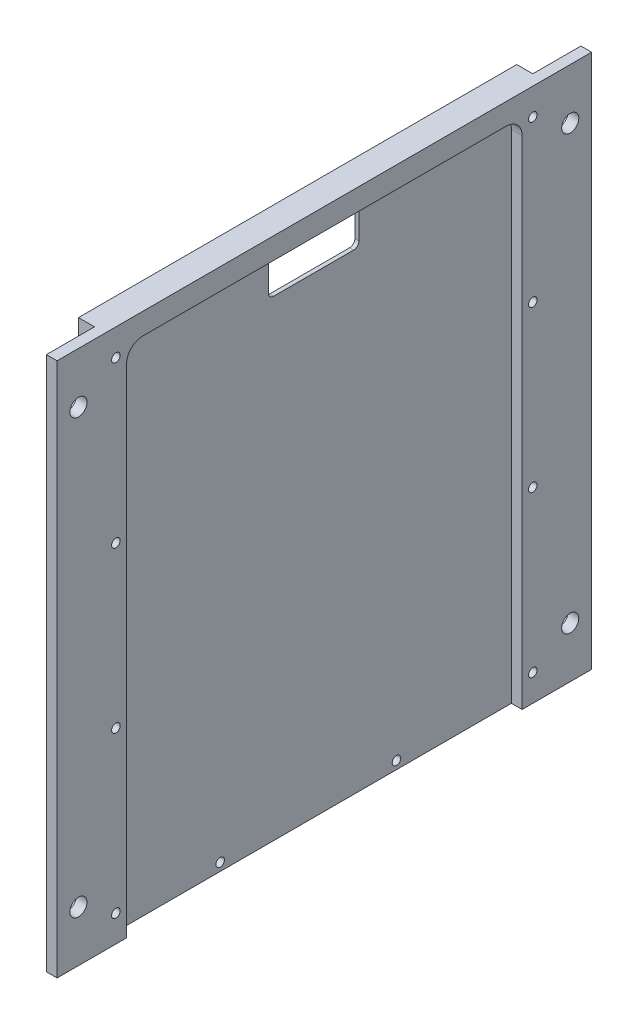
SolidWorks part; units mm, degrees
material "6061-T6 (SS)"
ref_plane "Front Plane" through (0, 0, 0) normal (0, 0, 1) x (1, 0, 0)
ref_plane "Top Plane" through (0, 0, 0) normal (0, 1, 0) x (1, 0, 0)
ref_plane "Right Plane" through (0, 0, 0) normal (1, 0, 0) x (0, 0, -1)
ref_plane "Plane1" through (4.25, 0, 0) normal (1, 0, 0) x (0, 0, -1)
sketch "Sketch1" plane through (4.25, 0, 0) normal (1, 0, 0) x (0, 0, -1)
  line L0 (-4.25, 0) -> (4.25, 0)
  line L1 (4.25, 0) -> (4.25, 227)
  line L2 (4.25, 227) -> (-4.25, 227)
  line L3 (-4.25, 227) -> (-4.25, 0)
  dimension "D1" = 227
  dimension "D2" = 8.5
  dimension "D3" = 4.25
  dimension "D4" = 227
extrude "Boss-Extrude1" add sketch "Sketch1" against normal blind 8.5
ref_plane "Plane2" through (-4.25, 0, 0) normal (-1, 0, 0) x (0, -1, 0)
sketch "Sketch2" plane through (-4.25, 0, 0) normal (-1, 0, 0) x (0, -1, 0)
  line L0 (-6.5, -87.25) -> (-6.5, -4.25)
  line L1 (-6.5, -4.25) -> (-220.5, -4.25)
  line L2 (-220.5, -4.25) -> (-220.5, -87.25)
  line L3 (-220.5, -87.25) -> (-227, -87.25)
  line L4 (-227, -87.25) -> (-227, -95.75)
  line L5 (-227, -95.75) -> (0, -95.75)
  line L6 (0, -95.75) -> (0, -87.25)
  line L7 (0, -87.25) -> (-6.5, -87.25)
  line L8 (0, -4.25) -> (-227, -4.25) construction
  dimension "D1" = 91.5
  dimension "D2" = 6.5
  dimension "D3" = 83
  dimension "D4" = 8.5
  dimension "D5" = 214
extrude "Boss-Extrude2" add sketch "Sketch2" against normal blind 2
sketch "Sketch3" plane through (-2.25, 0, 0) normal (1, 0, 0) x (0, 0, -1)
  line L0 (87.25, 0) -> (87.25, 227)
  line L1 (87.25, 227) -> (95.75, 227)
  line L2 (95.75, 227) -> (95.75, 0)
  line L3 (95.75, 0) -> (87.25, 0)
extrude "Boss-Extrude3" add sketch "Sketch3" along normal blind 6.5
ref_plane "Z_midplane" through (0, 113.5, 0) normal (0, 1, 0) x (1, 0, 0)
sketch "Sketch4" plane through (-4.25, 0, 0) normal (-1, 0, 0) x (0, 0, 1)
  line L0 (-4.75, 6.5) -> (-86.75, 6.5)
  line L1 (-86.75, 6.5) -> (-86.75, 220.5)
  line L2 (-86.75, 220.5) -> (-4.75, 220.5)
  line L3 (-4.75, 220.5) -> (-4.75, 6.5)
extrude "Boss-Extrude4" add sketch "Sketch4" along normal blind 3
sketch "Sketch5" plane through (-2.25, 0, 0) normal (1, 0, 0) x (0, 0, -1)
  line L0 (8.75, 10.5) -> (82.75, 10.5)
  line L1 (82.75, 10.5) -> (82.75, 216.5)
  line L2 (82.75, 216.5) -> (8.75, 216.5)
  line L3 (8.75, 216.5) -> (8.75, 10.5)
  line L4 (87.25, 6.5) -> (4.25, 6.5) construction
  line L5 (4.75, 6.5) -> (4.75, 220.5) construction
  line L6 (86.75, 220.5) -> (86.75, 6.5) construction
  line L7 (4.75, 220.5) -> (86.75, 220.5) construction
  dimension "D1" = 4
  dimension "D2" = 4
  dimension "D3" = 4
  dimension "D4" = 4
extrude "Cut-Extrude1" cut sketch "Sketch5" against normal through all
hole_wizard "M2x0.4 Tapped Hole1" positions "Sketch27" profile "Sketch26" tap size "M2x0.4" standard "ANSI Metric" end condition through all
sketch "Sketch27" plane through (-7.25, 0, 0) normal (-1, 0, 0) x (0, 0, 1)
  line L0 (-86.75, 6.5) -> (-4.75, 6.5) construction
  line L2 (-45.75, 10.5) -> (-45.75, 216.5) construction
  line L3 (-8.75, 10.5) -> (-82.75, 10.5) construction
  line L4 (-82.75, 216.5) -> (-8.75, 216.5) construction
  line L6 (-8.75, 113.5) -> (-82.75, 113.5) construction
  line L7 (-8.75, 216.5) -> (-8.75, 10.5) construction
  line L8 (-82.75, 10.5) -> (-82.75, 216.5) construction
  line L9 (-8.75, 11.5) -> (-4.75, 11.5) construction
  line L10 (-4.75, 6.5) -> (-4.75, 220.5) construction
  point P0 (-6.75, 11.5)
  point P31 (-6.75, 41.5)
  point P32 (-6.75, 71.5)
  point P33 (-6.75, 101.5)
  point P54 (-84.75, 11.5)
  point P55 (-84.75, 41.5)
  point P56 (-84.75, 71.5)
  point P57 (-84.75, 101.5)
  point P60 (-84.75, 125.5)
  point P61 (-84.75, 155.5)
  point P62 (-84.75, 185.5)
  point P63 (-84.75, 215.5)
  point P65 (-6.75, 125.5)
  point P66 (-6.75, 155.5)
  point P67 (-6.75, 185.5)
  point P68 (-6.75, 215.5)
  point P81 (-6.75, 11.5)
  dimension "D1" = 5
  dimension "D4" = 30
  dimension "D3" = 4
sketch "Sketch26" plane through (-7.25, 11.5, -6.75) normal (0, 1, 0) x (0, 0, 1)
  line L0 (0, 0) -> (0, 11.5)
  line L1 (0, 11.5) -> (0.8, 11.5)
  line L2 (0.8, 11.5) -> (0.8, 0)
  line L5 (0.8, 0) -> (0, 0)
  line L11 (0, -6.35) -> (0, 107.95) construction
  dimension "Thru Tap Drill Dia." = 1.6
  dimension "Thru Tap Drill Depth" = 11.5
cosmetic thread "Hole Thread1" parameters "D2"=2
cosmetic thread "Hole Thread2" parameters "D2"=2
cosmetic thread "Hole Thread3" parameters "D2"=2
cosmetic thread "Hole Thread4" parameters "D2"=2
cosmetic thread "Hole Thread5" parameters "D2"=2
cosmetic thread "Hole Thread6" parameters "D2"=2
cosmetic thread "Hole Thread7" parameters "D2"=2
cosmetic thread "Hole Thread8" parameters "D2"=2
cosmetic thread "Hole Thread9" parameters "D2"=2
cosmetic thread "Hole Thread10" parameters "D2"=2
cosmetic thread "Hole Thread11" parameters "D2"=2
cosmetic thread "Hole Thread12" parameters "D2"=2
cosmetic thread "Hole Thread13" parameters "D2"=2
cosmetic thread "Hole Thread14" parameters "D2"=2
cosmetic thread "Hole Thread15" parameters "D2"=2
cosmetic thread "Hole Thread16" parameters "D2"=2
fillet "Fillet2" radius 3 4 edges at (-4.75, 10.5, -8.75) (-4.75, 216.5, -82.75) (-4.75, 216.5, -8.75) (-4.75, 10.5, -82.75) tangent propagation no
fillet "Fillet12" radius 2 1 edges type face fillet first side face at (-6.5, 140.25, -86.75) second side face at (-4.75, 6.5, -45.8125)
ref_plane "Y_midplane" through (0, 0, -45.75) normal (0, 0, 1) x (1, 0, 0)
sketch "Sketch43" plane through (-7.25, 0, 0) normal (-1, 0, 0) x (0, 0, 1)
  line L0 (-45.75, 10.5) -> (-45.75, 216.5) construction
  line L1 (-27.75, 10.5) -> (-30.75, 10.5)
  line L2 (-27.75, 10.5) -> (-27.75, 216.5)
  line L3 (-27.75, 216.5) -> (-30.75, 216.5)
  line L4 (-30.75, 10.5) -> (-30.75, 216.5)
  line L5 (-11.75, 10.5) -> (-79.75, 10.5) construction
  line L6 (-79.75, 216.5) -> (-11.75, 216.5) construction
  line L7 (-63.75, 10.5) -> (-60.75, 10.5)
  line L8 (-63.75, 10.5) -> (-63.75, 216.5)
  line L9 (-63.75, 216.5) -> (-60.75, 216.5)
  line L10 (-60.75, 10.5) -> (-60.75, 216.5)
  dimension "D1" = 3
  dimension "D2" = 30
extrude "Boss-Extrude6" add sketch "Sketch43" against normal blind 3
sketch "Sketch44" plane through (-7.25, 0, 0) normal (-1, 0, 0) x (0, 0, 1)
  line L0 (-8.75, 213.5) -> (-8.75, 13.5) construction
  line L1 (-8.75, 35.8) -> (-82.75, 35.8)
  line L2 (-8.75, 35.8) -> (-8.75, 38.8)
  line L3 (-8.75, 38.8) -> (-82.75, 38.8)
  line L4 (-82.75, 35.8) -> (-82.75, 38.8)
  line L5 (-8.75, 75.8) -> (-82.75, 75.8)
  line L6 (-8.75, 75.8) -> (-8.75, 78.8)
  line L7 (-8.75, 78.8) -> (-82.75, 78.8)
  line L8 (-82.75, 75.8) -> (-82.75, 78.8)
  line L9 (-8.75, 103.5) -> (-82.75, 103.5)
  line L10 (-8.75, 103.5) -> (-8.75, 106.5)
  line L11 (-8.75, 106.5) -> (-82.75, 106.5)
  line L12 (-82.75, 103.5) -> (-82.75, 106.5)
  line L13 (-82.75, 13.5) -> (-82.75, 213.5) construction
  line L14 (-84.75, 6.5) -> (-4.75, 6.5) construction
  line L15 (-8.75, 113.5) -> (-82.75, 113.5) construction
  line L16 (-8.75, 191.2) -> (-8.75, 188.2)
  line L17 (-8.75, 191.2) -> (-82.75, 191.2)
  line L18 (-82.75, 191.2) -> (-82.75, 188.2)
  line L19 (-8.75, 188.2) -> (-82.75, 188.2)
  line L20 (-8.75, 151.2) -> (-8.75, 148.2)
  line L21 (-8.75, 151.2) -> (-82.75, 151.2)
  line L22 (-82.75, 151.2) -> (-82.75, 148.2)
  line L23 (-8.75, 148.2) -> (-82.75, 148.2)
  line L24 (-8.75, 123.5) -> (-8.75, 120.5)
  line L25 (-8.75, 123.5) -> (-82.75, 123.5)
  line L26 (-82.75, 123.5) -> (-82.75, 120.5)
  line L27 (-8.75, 120.5) -> (-82.75, 120.5)
  dimension "D1" = 3
  dimension "D2" = 29.3
  dimension "D3" = 40
  dimension "D4" = 100
extrude "Boss-Extrude7" add sketch "Sketch44" against normal up to surface (3 mm away) up to face at (-4.25, 113.5, -29.25)
fillet "Fillet4" radius 3 80 edges at (-5.75, 188.2, -8.75) (-5.75, 216.5, -60.75) (-5.75, 35.8, -82.75) (-5.75, 38.8, -82.75) (-5.75, 75.8, -82.75) (-5.75, 78.8, -82.75) (-5.75, 103.5, -82.75) (-5.75, 106.5, -82.75) (-5.75, 120.5, -82.75) (-5.75, 123.5, -82.75) (-5.75, 10.5, -60.75) (-5.75, 10.5, -63.75) (-5.75, 10.5, -27.75) (-5.75, 10.5, -30.75) (-5.75, 35.8, -8.75) (-5.75, 38.8, -8.75) (-5.75, 75.8, -8.75) (-5.75, 78.8, -8.75) (-5.75, 103.5, -8.75) (-5.75, 106.5, -8.75) (-5.75, 123.5, -8.75) (-5.75, 120.5, -8.75) (-5.75, 151.2, -8.75) (-5.75, 148.2, -8.75) (-5.75, 216.5, -27.75) (-5.75, 216.5, -63.75) (-5.75, 216.5, -30.75) (-5.75, 191.2, -8.75) (-5.75, 148.2, -82.75) (-5.75, 151.2, -82.75) (-5.75, 188.2, -82.75) (-5.75, 191.2, -82.75) (-5.75, 191.2, -60.75) (-5.75, 188.2, -60.75) (-5.75, 191.2, -63.75) (-5.75, 188.2, -63.75) (-5.75, 191.2, -27.75) (-5.75, 191.2, -30.75) (-5.75, 188.2, -27.75) (-5.75, 188.2, -30.75) (-5.75, 151.2, -27.75) (-5.75, 151.2, -30.75) (-5.75, 148.2, -27.75) (-5.75, 148.2, -30.75) (-5.75, 151.2, -60.75) (-5.75, 148.2, -60.75) (-5.75, 151.2, -63.75) (-5.75, 148.2, -63.75) (-5.75, 123.5, -27.75) (-5.75, 123.5, -30.75) (-5.75, 120.5, -27.75) (-5.75, 120.5, -30.75) (-5.75, 103.5, -27.75) (-5.75, 103.5, -30.75) (-5.75, 106.5, -27.75) (-5.75, 106.5, -30.75) (-5.75, 123.5, -60.75) (-5.75, 120.5, -60.75) (-5.75, 123.5, -63.75) (-5.75, 120.5, -63.75) (-5.75, 103.5, -60.75) (-5.75, 106.5, -60.75) (-5.75, 103.5, -63.75) (-5.75, 106.5, -63.75) (-5.75, 78.8, -30.75) (-5.75, 75.8, -27.75) (-5.75, 75.8, -30.75) (-5.75, 78.8, -27.75) (-5.75, 75.8, -60.75) (-5.75, 78.8, -60.75) (-5.75, 75.8, -63.75) (-5.75, 78.8, -63.75) (-5.75, 35.8, -27.75) (-5.75, 35.8, -30.75) (-5.75, 38.8, -27.75) (-5.75, 38.8, -30.75) (-5.75, 35.8, -63.75) (-5.75, 35.8, -60.75) (-5.75, 38.8, -63.75) (-5.75, 38.8, -60.75) tangent propagation no
sketch "Sketch50" plane through (-4.25, 0, 0) normal (1, 0, 0) x (0, 0, -1)
  line L0 (79.75, 216.5) -> (11.75, 216.5) construction
  line L1 (8.75, 213.5) -> (8.75, 13.5) construction
  line L2 (11.75, 10.5) -> (79.75, 10.5) construction
  line L3 (82.75, 13.5) -> (82.75, 213.5) construction
  line L4 (79.75, 216.5) -> (11.75, 216.5)
  line L5 (8.75, 213.5) -> (8.75, 13.5)
  line L6 (11.75, 10.5) -> (79.75, 10.5)
  line L7 (82.75, 13.5) -> (82.75, 213.5)
  arc A0 (82.75, 213.5) -> (79.75, 216.5) centre (79.75, 213.5) ccw construction
  arc A1 (11.75, 216.5) -> (8.75, 213.5) centre (11.75, 213.5) ccw construction
  arc A2 (8.75, 13.5) -> (11.75, 10.5) centre (11.75, 13.5) ccw construction
  arc A3 (79.75, 10.5) -> (82.75, 13.5) centre (79.75, 13.5) ccw construction
  arc A4 (82.75, 213.5) -> (79.75, 216.5) centre (79.75, 213.5) ccw
  arc A5 (11.75, 216.5) -> (8.75, 213.5) centre (11.75, 213.5) ccw
  arc A6 (8.75, 13.5) -> (11.75, 10.5) centre (11.75, 13.5) ccw
  arc A7 (79.75, 10.5) -> (82.75, 13.5) centre (79.75, 13.5) ccw
extrude "webExtrude" add sketch "Sketch50" against normal blind 0.75
sketch "Sketch51" plane through (-5, 0, 0) normal (-1, 0, 0) x (0, 0, 1)
  line L0 (-57.75, 216.5) -> (-33.75, 216.5) construction
  line L1 (-54.225, 216.5) -> (-37.275, 216.5)
  line L2 (-54.225, 216.5) -> (-54.225, 208.7)
  line L3 (-54.225, 208.7) -> (-37.275, 208.7)
  line L4 (-37.275, 216.5) -> (-37.275, 208.7)
  point P4 (-45.75, 216.5)
  dimension "D1" = 7.8
  dimension "D2" = 16.95
extrude "12pinCutout" cut sketch "Sketch51" against normal through all both and the other way through all
mirror "Mirror10" about plane through (0, 113.5, 0) normal (0, 1, 0) of "12pinCutout"
fillet "Fillet18" radius 1 8 edges at (-4.625, 216.5, -37.275) (-4.625, 216.5, -54.225) (-4.625, 208.7, -54.225) (-4.625, 208.7, -37.275) (-4.625, 10.5, -37.275) (-4.625, 18.3, -37.275) (-4.625, 18.3, -54.225) (-4.625, 10.5, -54.225)
hole_wizard "M2x0.4 Tapped Hole2" positions "Sketch45" profile "Sketch46" tap size "M2x0.4" standard "ANSI Metric" end condition through all
sketch "Sketch45" plane through (-7.25, 0, 0) normal (-1, 0, 0) x (0, 0, 1)
  line L0 (-44.75, 6.5) -> (-44.75, 220.5) construction
  line L1 (-84.75, 6.5) -> (-4.75, 6.5) construction
  line L20 (-4.75, 113.5) -> (-86.75, 113.5) construction
  line L21 (-4.75, 6.5) -> (-4.75, 220.5) construction
  line L23 (-62.25, 75.8) -> (-62.25, 78.8) construction
  line L24 (-79.75, 75.8) -> (-66.75, 75.8) construction
  line L25 (-66.75, 78.8) -> (-79.75, 78.8) construction
  line L27 (-60.75, 77.3) -> (-63.75, 77.3) construction
  line L28 (-60.75, 41.8) -> (-60.75, 72.8) construction
  line L29 (-63.75, 72.8) -> (-63.75, 41.8) construction
  line L30 (-79.75, 216.5) -> (-11.75, 216.5) construction
  line L31 (-87.25, 227) -> (-87.25, 0) construction
  point P2 (-61.25, 105)
  point P36 (-44.75, 6.5)
  point P68 (-28.25, 105)
  point P70 (-61.25, 122)
  point P71 (-28.25, 122)
  point P73 (-62.25, 77.3)
  point P92 (-27.25, 77.3)
  dimension "D1" = 4
  dimension "D2" = 0.5
  dimension "D3" = 16.5
  dimension "D4" = 17
sketch "Sketch46" plane through (-7.25, 105, -61.25) normal (0, 1, 0) x (0, 0, 1)
  line L0 (0, 0) -> (0, 11.5)
  line L1 (0, 11.5) -> (0.8, 11.5)
  line L2 (0.8, 11.5) -> (0.8, 0)
  line L5 (0.8, 0) -> (0, 0)
  line L11 (0, -6.35) -> (0, 107.95) construction
  dimension "Thru Tap Drill Dia." = 1.6
  dimension "Thru Tap Drill Depth" = 11.5
cosmetic thread "Hole Thread17" parameters "D2"=2
cosmetic thread "Hole Thread20" parameters "D2"=2
cosmetic thread "Hole Thread21" parameters "D2"=2
cosmetic thread "Hole Thread23" parameters "D2"=2
cosmetic thread "Hole Thread41" parameters "D2"=2
cosmetic thread "Hole Thread42" parameters "D2"=2
ref_plane "chamferStart" through (0, 212.5, 0) normal (0, 1, 0) x (1, 0, 0)
sketch "Sketch36" plane through (4.25, 0, 0) normal (1, 0, 0) x (0, 0, -1)
  line L1 (4.25, 207.45) -> (-1.25, 207.45)
  line L2 (4.25, 207.45) -> (4.25, 201.95)
  line L3 (4.25, 201.95) -> (-1.25, 201.95)
  line L4 (-1.25, 207.45) -> (-1.25, 201.95)
  line L5 (-4.25, 227) -> (-4.25, 0) construction
  line L6 (4.25, 207.45) -> (-1.25, 201.95) construction
  line L7 (4.25, 220.5) -> (87.25, 220.5) construction
  dimension "D1" = 13.05
  dimension "D2" = 5.5
  dimension "D3" = 5.5
  dimension "D4" = 8.5
extrude "Boss-Extrude5" add sketch "Sketch36" against normal up to surface (6.5 mm away) up to face at (-2.25, 12.3, -6.75)
ref_plane "Plane13" through (0, 113.5, 0) normal (0, 1, 0) x (1, 0, 0)
ref_plane "center_Y" through (0, 0, -45.75) normal (0, 0, 1) x (1, 0, 0)
ref_plane "center_Z" through (0, 113.5, 0) normal (0, 1, 0) x (1, 0, 0)
sketch "Sketch58" plane through (-2.25, 0, 0) normal (1, 0, 0) x (0, 0, -1)
  line L0 (11.75, 10.5) -> (79.75, 10.5) construction
  line L1 (43.25, 10.5) -> (48.25, 10.5)
  line L2 (43.25, 10.5) -> (43.25, 12)
  line L3 (43.25, 12) -> (48.25, 12)
  line L4 (48.25, 10.5) -> (48.25, 12)
  line L5 (87.25, 6.5) -> (4.25, 6.5) construction
  point P6 (45.75, 6.5)
  point P11 (45.75, 10.5)
  dimension "D1" = 5
  dimension "D2" = 5.5
extrude "Boss-Extrude9" add sketch "Sketch58" against normal up to surface (2.75 mm away) up to face at (-5, 18.775, -45.75)
sketch "Sketch63" plane through (0, 0, 0) normal (0, -1, 0) x (-1, 0, 0)
  line L1 (-4.25, 95.75) -> (7.9173, 95.75)
  line L2 (-4.25, 95.75) -> (-4.25, -4.25)
  line L3 (-4.25, -4.25) -> (7.9173, -4.25)
  line L4 (7.9173, 95.75) -> (7.9173, -4.25)
  dimension "D1" = 12.1673
  dimension "D2" = 100
extrude "Cut-Extrude28" cut sketch "Sketch63" against normal up to surface (120.5 mm away) up to face at (-6.125, 120.5, -45.75)
sketch "Sketch64" plane through (0, 227, 0) normal (0, 1, 0) x (1, 0, 0)
  line L1 (4.25, -4.25) -> (-12.9489, -4.25)
  line L2 (4.25, -4.25) -> (4.25, 100.8651)
  line L3 (4.25, 100.8651) -> (-12.9489, 100.8651)
  line L4 (-12.9489, -4.25) -> (-12.9489, 100.8651)
  dimension "D1" = 17.1989
  dimension "D2" = 105.1151
extrude "Cut-Extrude29" cut sketch "Sketch64" against normal up to surface (6.5 mm away) up to face at (-4.75, 220.5, -45.6875)
sketch "Sketch65" plane through (0, 220.5, 0) normal (0, 1, 0) x (1, 0, 0)
  line L1 (4.25, 95.75) -> (-2.25, 95.75)
  line L2 (4.25, 95.75) -> (4.25, 87.25)
  line L3 (4.25, 87.25) -> (-2.25, 87.25)
  line L4 (-2.25, 95.75) -> (-2.25, 87.25)
  line L5 (4.25, -4.25) -> (-2.25, -4.25)
  line L6 (4.25, -4.25) -> (4.25, 4.25)
  line L7 (4.25, 4.25) -> (-2.25, 4.25)
  line L8 (-2.25, -4.25) -> (-2.25, 4.25)
extrude "Cut-Extrude30" cut sketch "Sketch65" against normal through all
sketch "Sketch70" plane through (-2.25, 0, 0) normal (1, 0, 0) x (0, 0, -1)
  line L2 (45.75, 220.5) -> (45.75, 120.5) construction
  line L3 (95.75, 120.5) -> (95.75, 220.5) construction
  line L4 (-4.25, 220.5) -> (95.75, 220.5) construction
  line L5 (82.75, 120.5) -> (8.75, 120.5) construction
  point P2 (91.75, 130)
  point P3 (91.75, 211)
  point P12 (-0.25, 130)
  point P13 (-0.25, 211)
  dimension "D5" = 4
  dimension "D6" = 4
  dimension "D8" = 81
hole_wizard "M3 Clearance Hole2" positions "Sketch71" profile "Sketch72" hole size "M3" standard "ISO" end condition through all
sketch "Sketch71" plane through (-2.25, 0, 0) normal (1, 0, 0) x (0, 0, -1)
  point P6 (91.75, 211)
  point P9 (91.75, 130)
  point P12 (-0.25, 211)
  point P15 (-0.25, 130)
sketch "Sketch72" plane through (-2.25, 211, -91.75) normal (0, 1, 0) x (0, 0, -1)
  line L0 (0, 0) -> (0, 5)
  line L1 (0, 5) -> (1.6, 5)
  line L2 (1.6, 5) -> (1.6, 0)
  line L5 (1.6, 0) -> (0, 0)
  line L11 (0, -6.35) -> (0, 107.95) construction
  dimension "Thru Hole Dia." = 3.2
  dimension "Thru Hole Depth" = 5
equation "\"D2@Sketch56\"=\"D1@Sketch56\""
equation "\"D3@Sketch48\"=\"D2@Sketch48\""
